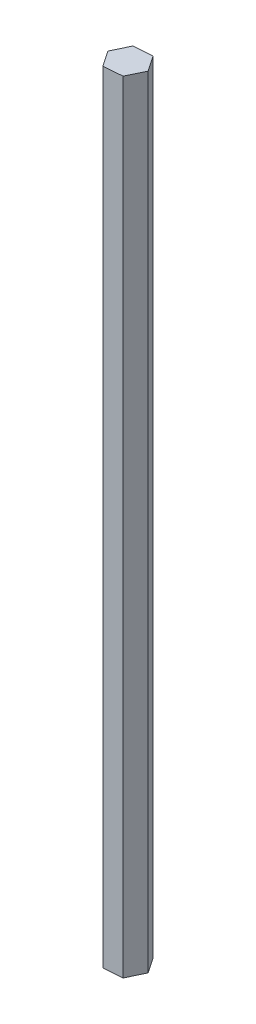
SolidWorks part; units mm, degrees
material "ALUMINUM 6061-T6"
ref_plane "Front Plane" through (0, 0, 0) normal (0, 0, 1) x (1, 0, 0)
ref_plane "Top Plane" through (0, 0, 0) normal (0, 1, 0) x (1, 0, 0)
ref_plane "Right Plane" through (0, 0, 0) normal (1, 0, 0) x (0, 0, -1)
sketch "Sketch1" plane through (0, 0, 0) normal (0, 1, 0) x (1, 0, 0)
  line L1 (7.3114, 0.554) -> (3.1759, 6.6089)
  line L2 (3.1759, 6.6089) -> (-4.1355, 6.0548)
  line L3 (-4.1355, 6.0548) -> (-7.3114, -0.554)
  line L4 (-7.3114, -0.554) -> (-3.1759, -6.6089)
  line L5 (-3.1759, -6.6089) -> (4.1355, -6.0548)
  line L6 (4.1355, -6.0548) -> (7.3114, 0.554)
  circle A1 centre (0, 0) radius 6.35 construction
extrude "Boss-Extrude1" add sketch "Sketch1" along normal mid plane 304.8
ref_axis "Axis1" through (0, -167.64, 0) along (0, 1, 0)
